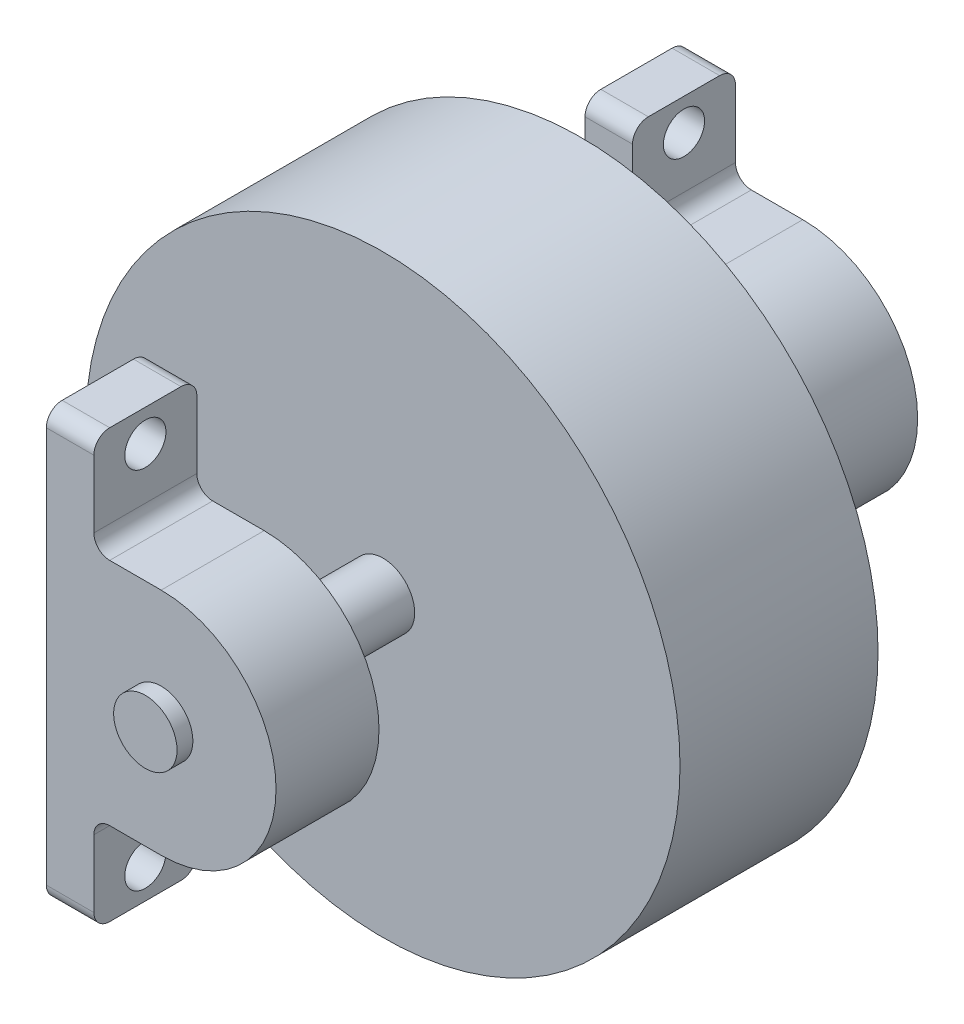
SolidWorks part; units mm, degrees
ref_plane "前视基准面" through (0, 0, 0) normal (0, 0, 1) x (1, 0, 0)
ref_plane "上视基准面" through (0, 0, 0) normal (0, 1, 0) x (1, 0, 0)
ref_plane "右视基准面" through (0, 0, 0) normal (1, 0, 0) x (0, 0, -1)
sketch "草图1" plane through (0, 0, 0) normal (0, 0, 1) x (1, 0, 0)
  circle A0 centre (0, 0) radius 37.5
  circle A1 centre (0, 0) radius 4
  dimension "D1" = 75
  dimension "D2" = 8
extrude "凸台-拉伸1" add sketch "草图1" against normal blind 12.5 and the other way blind 12.5 contours A0
extrude "凸台-拉伸2" add sketch "草图1<3>" along normal blind 42.5 and the other way blind 42.5 contours A1
sketch "草图1<3>" plane through (0, 0, 0) normal (0, 0, 1) x (1, 0, 0) same geometry as "草图1"
ref_plane "基准面4" through (0, 0, 40.5) normal (0, 0, 1) x (1, 0, 0)
sketch "草图2" plane through (0, 0, 40.5) normal (0, 0, 1) x (1, 0, 0)
  line L0 (0, 14.5) -> (0, -14.5)
  line L1 (0, 14.5) -> (-14.5, 14.5)
  line L2 (0, -14.5) -> (-14.5, -14.5)
  line L3 (-14.5, 14.5) -> (-14.5, -14.5)
  line L5 (-8.5, 27) -> (-14.5, 27)
  line L6 (-8.5, 27) -> (-8.5, -27)
  line L7 (-8.5, -27) -> (-14.5, -27)
  line L8 (-14.5, 27) -> (-14.5, -27)
  circle A0 centre (0, 0) radius 14.5
  dimension "D1" = 29
  dimension "D2" = 14.5
  dimension "D3" = 6
  dimension "D4" = 27
  dimension "D5" = 27
  dimension "D6" = 14.5
extrude "凸台-拉伸3" add sketch "草图2" against normal blind 13 contours A0 L6 L2 | A0 L1 L6 | A0 | L6 L7 L8 L5 region at (-6.4175, 13.6896, 40.5) region at (-6.4175, -13.6896, 40.5)
ref_plane "基准面5" through (0, 0, -40.5) normal (0, 0, -1) x (-1, 0, 0)
sketch "草图3" plane through (0, 0, -40.5) normal (0, 0, -1) x (-1, 0, 0)
  line L0 (0, -14.5) -> (0, 14.5)
  line L1 (0, -14.5) -> (14.5, -14.5)
  line L2 (0, 14.5) -> (14.5, 14.5)
  line L3 (14.5, -14.5) -> (14.5, 14.5)
  line L5 (8.5, -27) -> (14.5, -27)
  line L6 (8.5, -27) -> (8.5, 27)
  line L7 (8.5, 27) -> (14.5, 27)
  line L8 (14.5, -27) -> (14.5, 27)
  circle A0 centre (0, 0) radius 14.5
  dimension "D1" = 29
  dimension "D2" = 14.5
  dimension "D3" = 6
  dimension "D4" = 27
  dimension "D5" = 27
  dimension "D6" = 14.5
extrude "凸台-拉伸4" add sketch "草图3" against normal blind 13 contours A0 L6 L2 | A0 L1 L6 | A0 | L6 L7 L8 L5 region at (-6.4175, -13.6896, -40.5) region at (-6.4175, 13.6896, -40.5)
sketch "草图4" plane through (-8.5, 0, 0) normal (1, 0, 0) x (0, 0, -1)
  line L0 (27.5, 27) -> (40.5, 27) construction
  line L1 (40.5, 14.5) -> (40.5, 27) construction
  line L2 (27.5, -27) -> (40.5, -27) construction
  line L3 (40.5, -27) -> (40.5, -14.5) construction
  line L4 (-27.5, -27) -> (-40.5, -27) construction
  line L5 (-27.5, -14.5) -> (-27.5, -27) construction
  line L6 (-27.5, 27) -> (-27.5, 14.5) construction
  line L7 (-27.5, 27) -> (-40.5, 27) construction
  circle A0 centre (34, 23) radius 2.6
  circle A1 centre (34, -23) radius 2.6
  circle A2 centre (-34, -23) radius 2.6
  circle A3 centre (-34, 23) radius 2.6
  dimension "D2" = 5.2
  dimension "D4" = 5.2
  dimension "D7" = 5.2
  dimension "D8" = 5.2
  dimension "D1" = 4
  dimension "D3" = 6.5
  dimension "D5" = 4
  dimension "D6" = 6.5
  dimension "D9" = 4
  dimension "D10" = 6.5
  dimension "D11" = 6.5
  dimension "D12" = 4
extrude "切除-拉伸1" cut sketch "草图4" against normal through all
fillet "圆角1" radius 2 12 edges at (-11.5, 27, 27.5) (-11.5, 27, 40.5) (-8.5, 14.5, 34) (-8.5, -14.5, 34) (-11.5, -27, 40.5) (-11.5, -27, 27.5) (-11.5, -27, -27.5) (-11.5, 27, -27.5) (-11.5, 27, -40.5) (-11.5, -27, -40.5) (-8.5, -14.5, -34) (-8.5, 14.5, -34)
